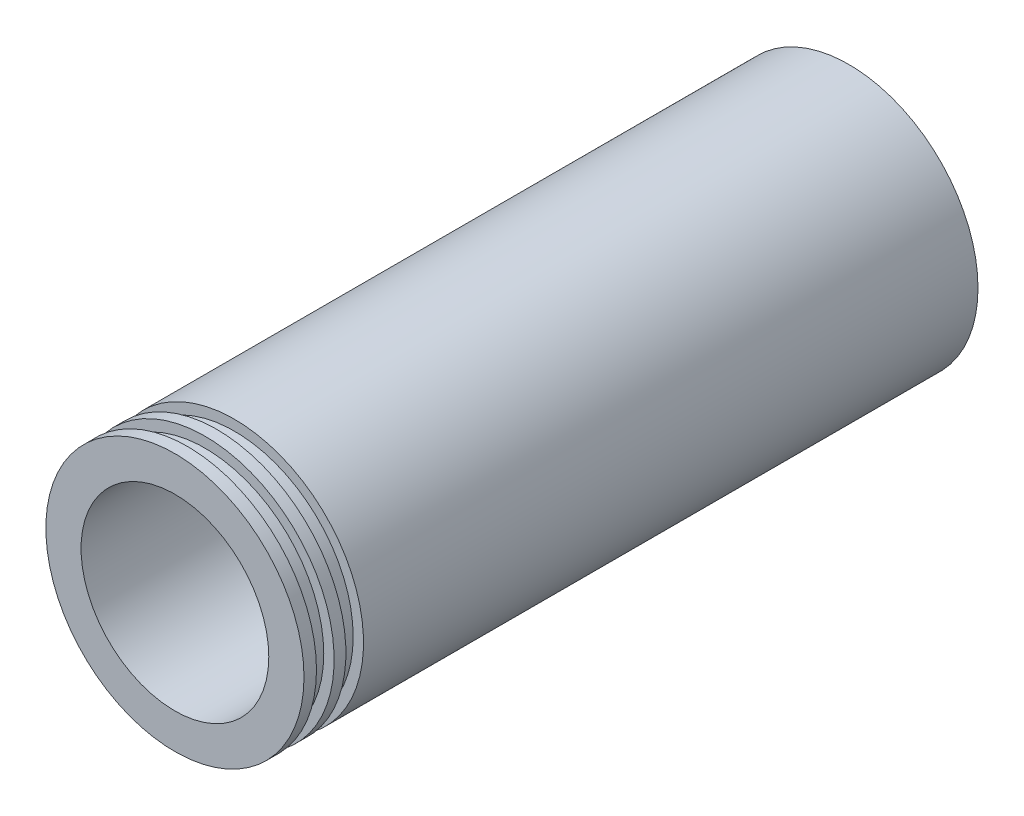
SolidWorks part; units mm, degrees
ref_plane "Front Plane" through (0, 0, 0) normal (0, 0, 1) x (1, 0, 0)
ref_plane "Top Plane" through (0, 0, 0) normal (0, 1, 0) x (1, 0, 0)
ref_plane "Right Plane" through (0, 0, 0) normal (1, 0, 0) x (0, 0, -1)
sketch "Sketch1" plane through (0, 0, 0) normal (0, 0, 1) x (1, 0, 0)
  circle A0 centre (0, 0) radius 34.925
  circle A1 centre (0, 0) radius 25.4
extrude "Boss-Extrude1" add sketch "Sketch1" along normal blind 182.372
sketch "Sketch2" plane through (0, 0, 0) normal (0, 1, 0) x (1, 0, 0)
  line L0 (25.4, 0) -> (-25.4, 0) construction
  circle A0 centre (0, -38.1) radius 5.588
  dimension "D1" = 38.1
extrude "Cut-Extrude1" cut sketch "Sketch2" against normal up to next
sketch "groove" plane through (0, 0, 0) normal (1, 0, 0) x (0, 0, -1)
  line L0 (-178.9939, 34.925) -> (-178.9939, 32.131)
  line L1 (-178.9939, 32.131) -> (-174.2314, 32.131)
  line L2 (-174.2314, 32.131) -> (-174.2187, 34.925)
  line L3 (-174.2187, 34.925) -> (-171.031, 34.925)
  line L4 (-171.031, 34.925) -> (-171.031, 32.131)
  line L5 (-171.031, 32.131) -> (-166.2685, 32.131)
  line L6 (-166.2685, 32.131) -> (-166.2685, 34.925)
  line L7 (-178.9939, 38.1) -> (-166.2685, 38.1)
  line L8 (-166.2685, 38.1) -> (-166.2685, 34.925)
  line L9 (-178.9939, 38.1) -> (-178.9939, 34.925)
  line L10 (-182.372, 34.925) -> (0, 34.925) construction
  dimension "D1" = 2.794
  dimension "D2" = 2.794
  dimension "D3" = 4.7625
  dimension "D4" = 4.7625
ref_plane "Plane1" through (0, 0, 171.031) normal (0, 0, 1) x (1, 0, 0)
sketch "groove path" plane through (0, 0, 171.031) normal (0, 0, 1) x (1, 0, 0)
  circle A0 centre (0, 0) radius 34.925 construction
  circle A1 centre (0, 0) radius 34.925
sweep "Cut-Sweep1" cut profiles "groove" path "groove path"
